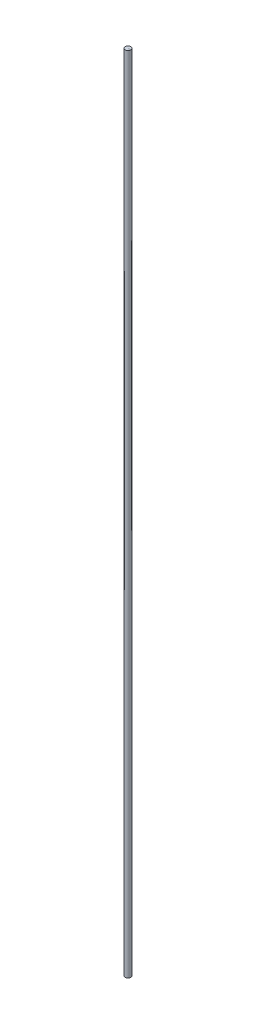
SolidWorks part; units mm, degrees
ref_plane "Front Plane" through (0, 0, 0) normal (0, 0, 1) x (1, 0, 0)
ref_plane "Top Plane" through (0, 0, 0) normal (0, 1, 0) x (1, 0, 0)
ref_plane "Right Plane" through (0, 0, 0) normal (1, 0, 0) x (0, 0, -1)
sketch "Sketch1" plane through (0, 0, 0) normal (0, 1, 0) x (1, 0, 0)
  line L0 (0, 0) -> (2, 0) construction
  circle A0 centre (0, 0) radius 2
  point P4 (0, 0)
  dimension "D1" = 4
extrude "Boss-Extrude1" add sketch "Sketch1" along normal blind 575
sketch "Sketch2" plane through (0, 575, 0) normal (0, 1, 0) x (1, 0, 0)
  line L0 (0, 0) -> (2, 0)
  line L1 (0, 0) -> (0, -0.1614)
  line L2 (0, -0.1614) -> (2, 0)
  circle A0 centre (0, 0) radius 2 construction
  point P0 (0, 0)
extrude "Boss-Extrude2" add sketch "Sketch2" along normal blind 0.0254
ref_plane "Plane1" through (0, 287.5, 0) normal (0, 1, 0) x (1, 0, 0)
mirror "Mirror1" about plane through (0, 287.5, 0) normal (0, 1, 0) of "Boss-Extrude2"
ref_axis "Axis1" through (0, 603.7779, 0) along (0, -1, 0)
